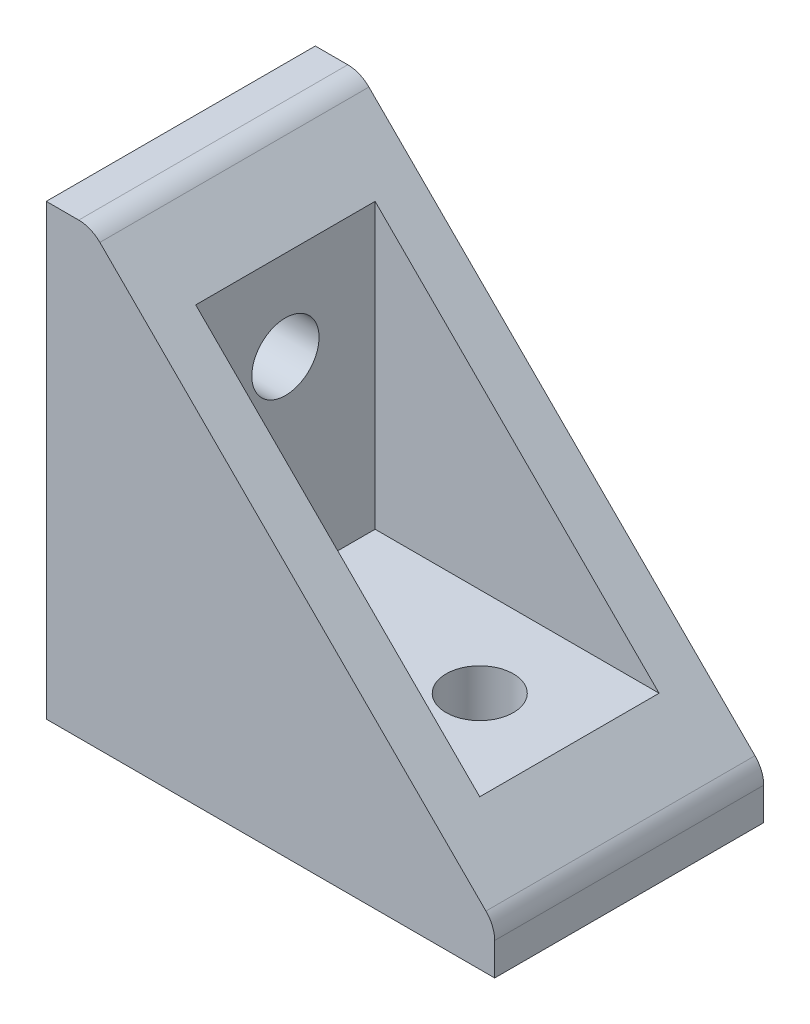
SolidWorks part; units mm, degrees
ref_plane "Спереди" through (0, 0, 0) normal (0, 0, 1) x (1, 0, 0)
ref_plane "Сверху" through (0, 0, 0) normal (0, 1, 0) x (1, 0, 0)
ref_plane "Справа" through (0, 0, 0) normal (1, 0, 0) x (0, 0, -1)
sketch "Эскиз3" plane through (0, 0, 0) normal (0, 0, 1) x (1, 0, 0)
  line L0 (0, 0) -> (30, 0)
  line L1 (30, 0) -> (30, 3)
  line L2 (30, 3) -> (3, 30)
  line L3 (3, 30) -> (0, 30)
  line L4 (0, 30) -> (0, 0)
  dimension "D1" = 3
  dimension "D2" = 30
  dimension "D3" = 30
extrude "Бобышка-Вытянуть1" add sketch "Эскиз3" along normal blind 9 and the other way blind 9
sketch "Эскиз5" plane through (0, 0, 9) normal (0, 0, 1) x (1, 0, 0)
  line L0 (0, 0) -> (16.5, 16.5) construction
  line L1 (30, 3) -> (3, 30) construction
sketch "Эскиз6" plane through (0, 0, 0) normal (-1, 0, 0) x (0, 0, 1)
  line L0 (-9, 30) -> (9, 30) construction
  line L2 (-9, 0) -> (9, 0) construction
  circle A0 centre (0, 20) radius 2.25
  point P6 (0, 30)
  dimension "D1" = 4.5
  dimension "D2" = 20
extrude "Вырез-Вытянуть1" cut sketch "Эскиз6" against normal through all
ref_plane "Плоскость1" through (0, 0, 0) normal (0.7071, -0.7071, 0) x (0, 0, -1)
sketch "Эскиз7" plane through (0, 30, 0) normal (0, 1, 0) x (1, 0, 0)
  line L1 (7, 6) -> (27, 6)
  line L2 (7, 6) -> (7, -6)
  line L3 (7, -6) -> (27, -6)
  line L4 (27, 6) -> (27, -6)
  line L5 (3, 9) -> (0, 9) construction
  line L6 (3, -9) -> (0, -9) construction
  line L7 (0, 9) -> (0, -9) construction
  line L8 (30, 9) -> (30, -9) construction
  point P8 (1.5, 9)
  dimension "D1" = 3
  dimension "D2" = 3
  dimension "D3" = 7
  dimension "D4" = 3
extrude "Вырез-Вытянуть2" cut sketch "Эскиз7" against normal blind 23
sketch "Эскиз8" plane through (0, 0, 0) normal (-1, 0, 0) x (0, 0, 1)
  line L0 (-9, 0) -> (9, 0) construction
  line L1 (-3, 0) -> (3, 0)
  line L2 (-3, 0) -> (-3, 14)
  line L3 (-3, 14) -> (3, 14)
  line L4 (3, 0) -> (3, 14)
  circle A0 centre (0, 20) radius 2.25 construction
  point P6 (0, 14)
  dimension "D1" = 6
  dimension "D2" = 6
extrude "Бобышка-Вытянуть2" add sketch "Эскиз8" along normal blind 3
mirror "Зеркальное отражение1" about plane through (0, 0, 0) normal (0.7071, -0.7071, 0) of "Бобышка-Вытянуть2", "Вырез-Вытянуть1"
fillet "Скругление1" radius 2 2 edges at (30, 3, 0) (3, 30, 0)
